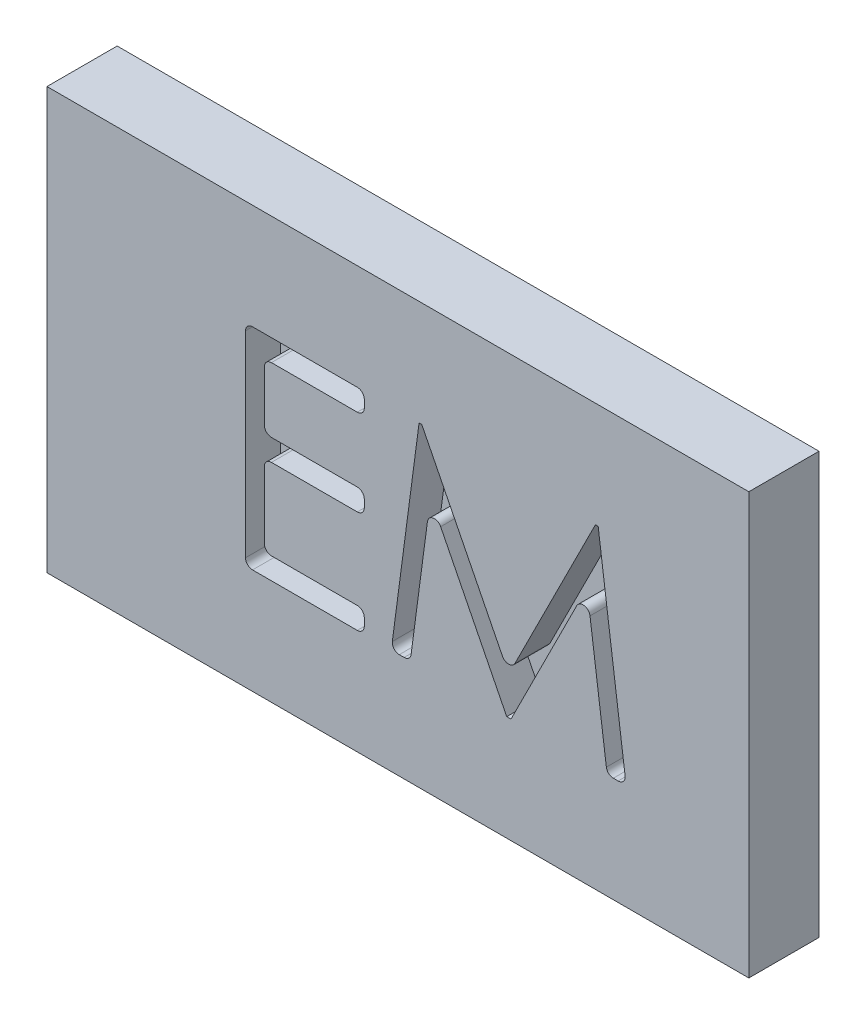
SolidWorks part; units mm, degrees
ref_plane "Front Plane" through (0, 0, 0) normal (0, 0, 1) x (1, 0, 0)
ref_plane "Top Plane" through (0, 0, 0) normal (0, 1, 0) x (1, 0, 0)
ref_plane "Right Plane" through (0, 0, 0) normal (1, 0, 0) x (0, 0, -1)
sketch "Sketch3" plane through (0, 0, 0) normal (0, 0, 1) x (1, 0, 0)
  line L1 (-50, 0) -> (50, 0)
  line L2 (-50, 0) -> (-50, 60)
  line L3 (-50, 60) -> (50, 60)
  line L4 (50, 0) -> (50, 60)
  point P5 (0, 0)
  point P6 (0, 0)
  dimension "D1" = 60
  dimension "D2" = 100
extrude "Boss-Extrude3" add sketch "Sketch3" along normal blind 10 contours L3 L4 L1 L2
sketch "Sketch1" plane through (0, 0, 0) normal (0, 0, 1) x (1, 0, 0)
  line L0 (-25.5589, 15) -> (25.5589, 15) construction
  text T0 "EM" font "Century Gothic" height 30
  point P2 (18.9347, 30)
  point P3 (-25.5589, 30)
  point P5 (0, 15)
  point P7 (0, 0)
  point P8 (0, 0)
  point P9 (-3.7984, 25.8957)
  point P10 (-46.8015, 37.8936)
  point P11 (0, 0)
  point P12 (0, 30)
  point P13 (0, 0)
  point P14 (0, 0)
  dimension "D1" = 15
extrude "Boss-Extrude1" [suppressed] add sketch "Sketch1" along normal blind 5
sketch "Sketch2" [suppressed] plane through (-3.141, 0, 0) normal (1, 0, 0) x (0, 0, -1)
  line L4 (0, 30) -> (0, 31.0256)
  line L5 (0, 31.0256) -> (-5, 31.0256)
  line L6 (-5, 31.0256) -> (-5, 30)
  line L7 (-5, 30) -> (0, 30)
  line L8 (0, 30) -> (0, 31.0256)
  line L9 (0, 31.0256) -> (-5, 31.0256)
  line L10 (-5, 31.0256) -> (-5, 30)
  line L11 (-5, 30) -> (0, 30)
  dimension "D1" = 0
extrude "Boss-Extrude2" [suppressed] add sketch "Sketch2" along normal up to surface (2.3214 mm away)
extrude "Cut-Extrude1" cut sketch "Sketch1<2>" against normal blind 5 from surface starting at face at (0, 30, 10)
sketch "Sketch1<2>" plane through (0, 0, 0) normal (0, 0, 1) x (1, 0, 0) same geometry as "Sketch1"
fillet "Fillet1" radius 1 19 edges at (32.518, 15, 7.5) (29.8137, 15, 7.5) (26.9411, 36.5865, 7.5) (15.7873, 20.3846, 7.5) (4.6334, 36.6346, 7.5) (1.7668, 15, 7.5) (-0.9435, 15, 7.5) (-21.7127, 15, 7.5) (-4.7897, 15, 7.5) (-4.7897, 18.0769, 7.5) (-19.0204, 18.0769, 7.5) (-4.7897, 29.6154, 7.5) (-4.7897, 32.6923, 7.5) (-19.0204, 29.6154, 7.5) (-19.0204, 32.6923, 7.5) (-21.7127, 45, 7.5) (-19.0204, 41.9231, 7.5) (-4.7897, 41.9231, 7.5) (-4.7897, 45, 7.5)
